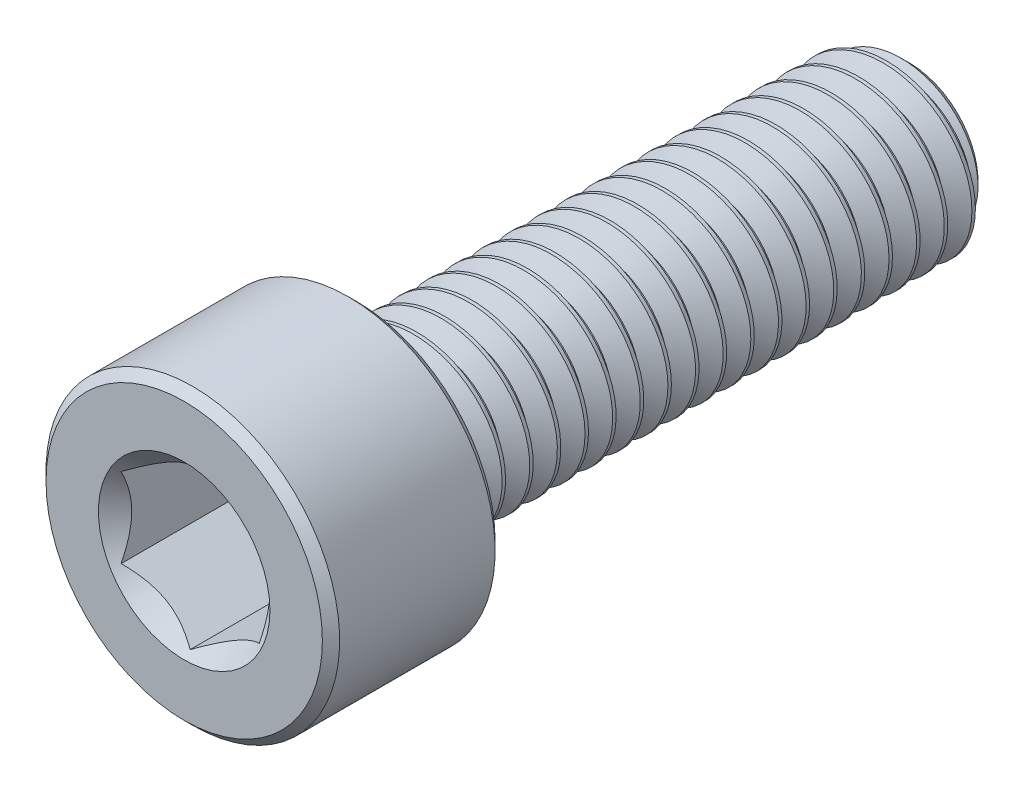
SolidWorks part; units mm, degrees
ref_plane "Front Plane" through (0, 0, 0) normal (0, 0, 1) x (1, 0, 0)
ref_plane "Top Plane" through (0, 0, 0) normal (0, 1, 0) x (1, 0, 0)
ref_plane "Right Plane" through (0, 0, 0) normal (1, 0, 0) x (0, 0, -1)
sketch "Sketch1" plane through (0, 0, 0) normal (1, 0, 0) x (0, 0, -1)
  line L0 (-10.5, 0) -> (10.5, 0) construction
  line L1 (10.5, 0) -> (10.5, 1.9804) construction
  line L2 (10.5, 1.9804) -> (9.9804, 2.5) construction
  line L3 (9.9804, 2.5) -> (9.9, 2.5) construction
  line L4 (9.9, 2.5) -> (-5.5, 2.5) construction
  line L5 (-5.5, 2.5) -> (-5.5, 4.25) construction
  line L6 (-5.5, 4.25) -> (-10.5, 4.25) construction
  line L7 (-10.5, 4.25) -> (-10.5, 0) construction
  line L8 (10.5, 1.9804) -> (10.5, 2.5) construction
  line L9 (10.45, 2.5866) -> (10.85, 1.8938) construction
  line L10 (10.85, 1.8938) -> (11.25, 2.5866) construction
  line L11 (11.25, 2.5866) -> (10.45, 2.5866) construction
  line L12 (10.85, 2.5866) -> (10.85, 2.5) construction
  line L13 (10.85, 1.8938) -> (10.85, 1.9804) construction
  line L14 (10.8, 1.9804) -> (10.9, 1.9804) construction
  line L15 (10.5, 2.5) -> (11.2, 2.5) construction
  line L16 (10.475, 2.5433) -> (11.225, 2.5433) construction
  line L17 (10.5, 0) -> (10.5, -2.5) construction
  line L18 (-5.75, 4.25) -> (-5.5, 4) construction
  line L19 (-10.25, 4.25) -> (-10.5, 4) construction
  line L20 (-5.5, 2.5) -> (-5.5, 0) construction
  line L21 (-5.5, 1.25) -> (-0.1667, 1.25) construction
  line L22 (-0.1667, 1.25) -> (5.1667, 1.25) construction
  line L23 (5.1667, 1.25) -> (10.5, 1.25) construction
  line L24 (-0.1667, 1.25) -> (-0.1667, 2.5) construction
  line L25 (-0.1667, 2.5) -> (-0.1667, 4.25) construction
  line L26 (5.1667, 1.25) -> (5.1667, 4.25) construction
  point P0 (-10.5, 2)
  point P3 (8.5, 2.5)
  point P4 (0, 0)
  point P18 (5.1667, 2.5)
  point P22 (10.85, 1.9804)
  point P24 (9.9, 2.5)
  point P25 (10.85, 2.5)
  point P28 (10.85, 2.5433)
  point P29 (8.5, -2.5)
  point P30 (-0.1667, 2.5)
  point P31 (-8, 4.25)
  point P37 (-6.375, 4.25)
  point P38 (-10.125, 4.25)
  point P45 (-0.1667, 1.25)
  point P46 (5.1667, 1.25)
  dimension "D2" = 0.1
  dimension "D7" = 0.25
  dimension "D8" = 0.25
  dimension "D9" = 0.25
  dimension "D10" = 0.125
  dimension "D11" = 0.625
  dimension "Drive Size" = 4
  dimension "Head Diameter" = 8.5
  dimension "Head Height" = 5
  dimension "Thread Pitch" = 0.8
  dimension "Thread Dia" = 5
  dimension "Length" = 16
  dimension "D12" = 0.6
  dimension "D4" = 2
  dimension "D3" = 45
sketch "Sketch2" plane through (0, 0, 0) normal (1, 0, 0) x (0, 0, -1)
  line L0 (-10.5, 0) -> (-10.5, 4)
  line L1 (-10.25, 4.25) -> (-5.75, 4.25)
  line L2 (-5.5, 4) -> (-5.5, 2.75)
  line L4 (9.9804, 2.5) -> (10.5, 1.9804)
  line L5 (10.5, 1.9804) -> (10.5, 0)
  line L6 (-5.5, 4.25) -> (-10.5, 4.25) construction
  line L7 (10.5, 0) -> (-10.5, 0)
  line L8 (-10.25, 4.25) -> (-10.5, 4) construction
  line L10 (-10.25, 4.25) -> (-10.5, 4)
  line L14 (-5.75, 4.25) -> (-5.5, 4) construction
  line L16 (-5.75, 4.25) -> (-5.5, 4)
  line L17 (-5.5, 2.5) -> (-5.5, 4.25) construction
  line L19 (-5.25, 2.5) -> (9.9804, 2.5)
  line L20 (9.9, 2.5) -> (-5.5, 2.5) construction
  arc A1 (-5.5, 2.75) -> (-5.25, 2.5) centre (-5.25, 2.75) ccw
  dimension "D3" = 0.25
revolve "Revolve1" add sketch "Sketch2" angle 360 about L7
sketch "Sketch3" plane through (0, 0, 10.5) normal (0, 0, 1) x (1, 0, 0)
  line L1 (2, -1.1547) -> (2, 1.1547)
  line L2 (2, 1.1547) -> (0, 2.3094)
  line L3 (0, 2.3094) -> (-2, 1.1547)
  line L4 (-2, 1.1547) -> (-2, -1.1547)
  line L5 (-2, -1.1547) -> (0, -2.3094)
  line L6 (0, -2.3094) -> (2, -1.1547)
  circle A0 centre (0, 0) radius 2 construction
  circle A1 centre (0, 0) radius 4.25 construction
  circle A2 centre (0, 0) radius 4.25 construction
  circle A3 centre (0, 0) radius 2.3094 construction
  point P13 (0, 0)
  dimension "D1" = 4.6188
extrude "Cut-Extrude1" cut sketch "Sketch3" against normal offset from surface (4 mm away) 1 up to face at (0, 4, 5.5)
sketch "Sketch4" plane through (0, 0, 10.5) normal (0, 0, 1) x (1, 0, 0)
  circle A0 centre (0, 0) radius 2.4826
  dimension "D1" = 4.9652
extrude "Cut-Extrude2" cut sketch "Sketch4" against normal up to vertex (2.5 mm away) draft 45 up to point (0, 4.25, 8)
sketch "Sketch11" plane through (0, 0, 0) normal (1, 0, 0) x (0, 0, -1)
  line L0 (-10.5, 0) -> (10.5, 0) construction
  line L1 (-10.5, 0) -> (10.5, 0) construction
  line L2 (-2.5, 0) -> (-2.5, 2.5) construction
  line L3 (9.9, 2.5) -> (-5.5, 2.5) construction
  line L4 (7.5, 0) -> (7.5, 2.5) construction
  line L6 (10.5, 1.9804) -> (10.5, 2.5) construction
  point P2 (-2.5, 0)
  point P3 (7.5, 0)
  dimension "D1" = 3
  dimension "D2" = 3
sketch "Sketch6" plane through (0, 0, -10.5) normal (0, 0, -1) x (-1, 0, 0)
  circle A0 centre (0, 0) radius 2.5
curve "Helix/Spiral1" pitch 0.8 height 16.8 radius 2.5 centre (0, 0, -10.5) axis (0, 0, 1) start towards (0, 1, 0)
sketch "Sketch10" plane through (0, 0, 0) normal (1, 0, 0) x (0, 0, -1)
  line L0 (-5.25, -4.25) -> (-5.25, 4.25)
  line L5 (-10.5, 0) -> (10.5, 0) construction
  line L6 (-5.25, 2.5) -> (-5.25, -2.5) construction
  point P3 (-5.25, 0)
split "Split1" trim tools "Sketch10" bodies to split 106 resulting bodies 114 115
sketch "Sketch7" plane through (0, 0, 0) normal (1, 0, 0) x (0, 0, -1)
  line L0 (10.475, 2.5433) -> (11.225, 2.5433)
  line L1 (11.225, 2.5433) -> (10.9, 1.9804)
  line L2 (10.9, 1.9804) -> (10.8, 1.9804)
  line L3 (10.8, 1.9804) -> (10.475, 2.5433)
sweep "Cut-Sweep1" cut profiles "Sketch7" path "Helix/Spiral1" align with end faces yes
sketch "Sketch8" plane through (0, 0, 0) normal (1, 0, 0) x (0, 0, -1)
  line L0 (-5.5, 0) -> (-5.5, 2.5)
  line L1 (-5.25, -2.5) -> (-5.25, 2.5) construction
  line L2 (-5.5, 2.5) -> (-5.25, 2.5)
  line L4 (-5.25, 2.5) -> (-3.8066, 0)
  line L5 (-3.8066, 0) -> (-5.5, 0)
  line L6 (9.9, 2.5) -> (-5.5, 2.5) construction
  line L7 (-10.5, 0) -> (10.5, 0) construction
  dimension "D1" = 60
revolve "Revolve2" add sketch "Sketch8" angle 360 about L5
equation "\"D2@Sketch1\" = \"Thread Pitch@Sketch1\" / 8"
equation "\"D4@Helix/Spiral1\" = \"Thread Pitch@Sketch1\""
equation "\"D7@Sketch1\" = \"Head Height@Sketch1\" * .05"
equation "\"D8@Sketch1\"=\"D7@Sketch1\""
equation "\"D9@Sketch1\"=\"D7@Sketch1\""
equation "\"D10@Sketch1\"=\"D7@Sketch1\"/2"
equation "\"D11@Sketch1\"=\"D10@Sketch1\"*5"
equation "\"D4@Sketch1\"=\"Thread Pitch@Sketch1\"*2.5"
equation "\"D12@Sketch1\"=\"Thread Pitch@Sketch1\"*.75"
equation "\"D3@Helix/Spiral1\"=\"Length@Sketch1\"+\"Thread Pitch@Sketch1\""
equation "\"D3@Sketch2\"=\"Thread Dia@Sketch1\"*0.05"
equation "\"D1@Sketch11\"=\"Length@Sketch1\"*0.1875"
equation "\"D2@Sketch11\"=\"D1@Sketch11\""
equation "\"D1@Sketch4\"=\"D1@Sketch3\"*1.075"
